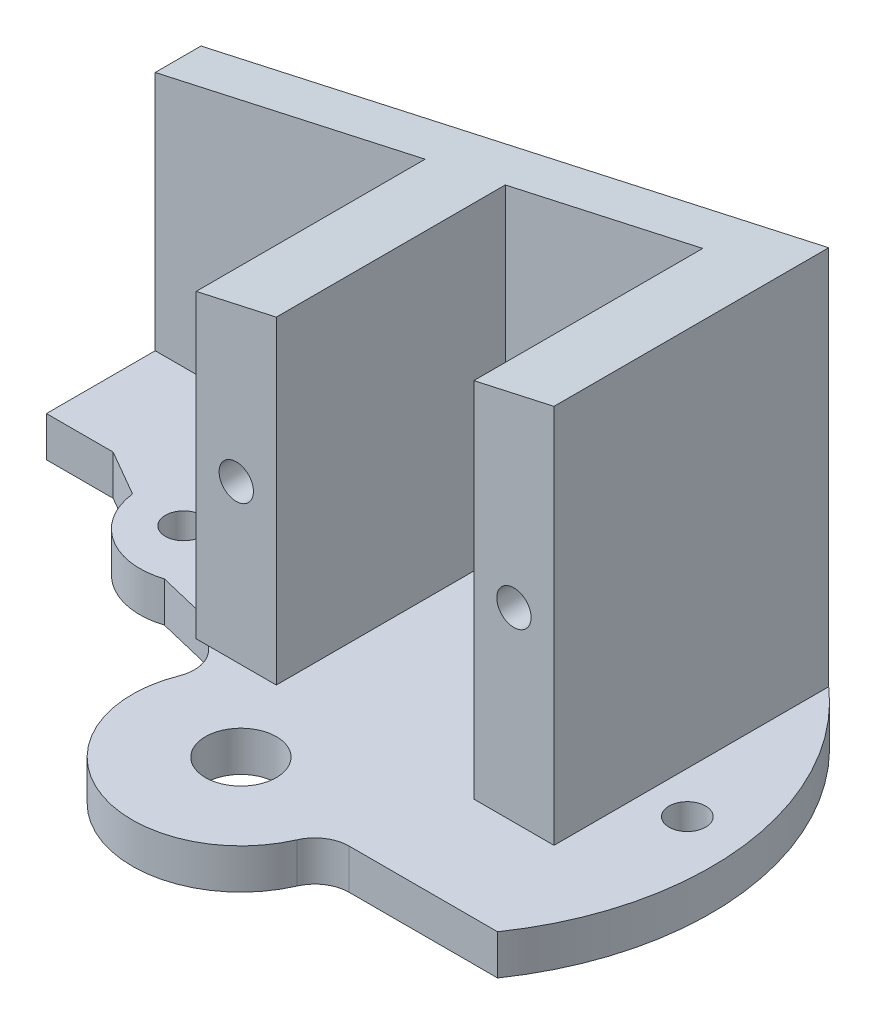
SolidWorks part; units mm, degrees
ref_plane "Alzado" through (0, 0, 0) normal (0, 0, 1) x (1, 0, 0)
ref_plane "Planta" through (0, 0, 0) normal (0, 1, 0) x (1, 0, 0)
ref_plane "Vista lateral" through (0, 0, 0) normal (1, 0, 0) x (0, 0, -1)
sketch "Croquis1" plane through (0, 0, 0) normal (0, 1, 0) x (1, 0, 0)
  line L0 (-35, 32.5) -> (35, -32.5) construction
  line L1 (-35, 32.5) -> (35, 32.5)
  line L2 (-35, 32.5) -> (-35, -32.5)
  line L3 (-35, -32.5) -> (35, -32.5)
  line L4 (35, 32.5) -> (35, -32.5)
  dimension "D1" = 70
  dimension "D2" = 65
extrude "Extruir1" add sketch "Croquis1" along normal blind 3.5
sketch "Croquis2" plane through (0, 3.5, 0) normal (0, 1, 0) x (1, 0, 0)
  line L0 (0, 32.5) -> (0, -32.5) construction
  line L1 (35, 32.5) -> (-35, 32.5) construction
  line L2 (-35, -32.5) -> (35, -32.5) construction
  circle A0 centre (0, -17.5) radius 3.1
  dimension "D1" = 6.2
  dimension "D2" = 15
extrude "Extruir2" cut sketch "Croquis2" against normal blind 5
sketch "Croquis3" plane through (0, 3.5, 0) normal (0, 1, 0) x (1, 0, 0)
  line L0 (0, -32.5) -> (0, 32.5) construction
  line L1 (-35, -32.5) -> (35, -32.5) construction
  line L2 (35, 32.5) -> (-35, 32.5) construction
  line L3 (-32.9868, -32.5) -> (-32.9868, 32.5) construction
  line L4 (-32.9868, 1.5) -> (-12.9615, 1.5)
  line L5 (18.8496, -32.5) -> (18.8496, 32.5) construction
  line L6 (-32.9868, 3.5) -> (18.8496, 3.5) construction
  line L7 (-32.9868, 2) -> (0, 2) construction
  line L8 (-32.9868, 11.5) -> (18.8496, 11.5) construction
  line L9 (0, -17.5) -> (-14.8492, -2.6508) construction
  line L10 (0, -17.5) -> (14.8492, -2.6508) construction
  line L11 (0, 2) -> (18.8496, 2) construction
  line L12 (-32.9868, 2) -> (18.8496, 2) construction
  line L13 (-32.9868, 12) -> (18.8496, 12)
  line L14 (-5.3033, -12.1967) -> (-16.2635, -1.2365) construction
  line L15 (12.9615, 1.5) -> (18.8496, 1.5)
  line L16 (-32.9868, 1.5) -> (18.8496, 1.5) construction
  line L17 (7.9844, -18) -> (22.9946, -18)
  line L18 (-5.9993, -12.2078) -> (-16.6132, -1.5939)
  line L19 (0, -17.5) -> (23, -17.5) construction
  line L20 (7.5, -17.5) -> (23, -17.5) construction
  line L21 (-5.6569, -12.5503) -> (-16.617, -1.5901) construction
  line L22 (7.5, -18) -> (23, -18) construction
  line L23 (-32.9868, 12) -> (-32.9868, 1.5)
  line L24 (18.8496, 12) -> (18.8496, 1.5)
  line L25 (-34.4868, 13.5) -> (20.3496, 13.5)
  line L26 (20.3496, 13.5) -> (20.3496, 0)
  line L27 (17.1464, 0) -> (20.3496, 0)
  line L28 (9.2871, -19.5) -> (24.4182, -19.5)
  line L29 (-7.9812, -12.3473) -> (-18.6805, -1.6479)
  line L30 (-34.4868, 0) -> (-17.1464, 0)
  line L31 (-34.4868, 13.5) -> (-34.4868, 0)
  circle A0 centre (0, -17.5) radius 21 construction
  circle A1 centre (0, -17.5) radius 7.5 construction
  arc A2 (-12.9615, 1.5) -> (-16.6132, -1.5939) centre (0, -17.5) ccw
  circle A3 centre (0, -17.5) radius 23 construction
  arc A4 (-5.9993, -12.2078) -> (7.9844, -18) centre (0, -17.5) ccw
  arc A5 (22.9946, -18) -> (12.9615, 1.5) centre (0, -17.5) ccw
  arc A6 (24.4182, -19.5) -> (17.1464, 0) centre (0, -17.5) ccw
  arc A7 (-7.9812, -12.3473) -> (9.2871, -19.5) centre (0, -17.5) ccw
  arc A8 (-17.1464, 0) -> (-18.6805, -1.6479) centre (0, -17.5) ccw
  dimension "D3" = 42
  dimension "D8" = 15
  dimension "D9" = 46
  dimension "D14" = 0.5
  dimension "D2" = 51.8364
  dimension "D6" = 90
  dimension "D7" = 45
  dimension "D1" = 32.9868
  dimension "D4" = 1.5
  dimension "D5" = 9.5
  dimension "D10" = 2
  dimension "D11" = 0.5
  dimension "D12" = 0.5
  dimension "D13" = 0.5
  dimension "D15" = 1.5
extrude "Extruir3" add sketch "Croquis3" along normal blind 10
sketch "Croquis4" plane through (0, 3.5, 0) normal (0, 1, 0) x (1, 0, 0)
  line L0 (-34.4868, 0) -> (-17.1464, 0) construction
  line L1 (-34.4868, 13.5) -> (-34.4868, 0) construction
  line L2 (20.3496, 13.5) -> (-34.4868, 13.5) construction
  line L3 (20.3496, 0) -> (20.3496, 13.5) construction
  line L4 (17.1464, 0) -> (20.3496, 0) construction
  line L5 (9.2871, -19.5) -> (24.4182, -19.5) construction
  line L6 (-18.6805, -1.6479) -> (-7.9812, -12.3473) construction
  line L7 (-34.4868, 0) -> (-17.1464, 0)
  line L8 (-34.4868, 13.5) -> (-34.4868, 0)
  line L9 (20.3496, 13.5) -> (-34.4868, 13.5)
  line L10 (20.3496, 0) -> (20.3496, 13.5)
  line L11 (17.1464, 0) -> (20.3496, 0)
  line L12 (9.2871, -19.5) -> (24.4182, -19.5)
  line L13 (-18.6805, -1.6479) -> (-7.9812, -12.3473)
  arc A0 (-17.1464, 0) -> (-18.6805, -1.6479) centre (0, -17.5) ccw construction
  arc A1 (24.4182, -19.5) -> (17.1464, 0) centre (0, -17.5) ccw construction
  arc A2 (-7.9812, -12.3473) -> (9.2871, -19.5) centre (0, -17.5) ccw construction
  arc A3 (-17.1464, 0) -> (-18.6805, -1.6479) centre (0, -17.5) ccw
  arc A4 (24.4182, -19.5) -> (17.1464, 0) centre (0, -17.5) ccw
  arc A5 (-7.9812, -12.3473) -> (9.2871, -19.5) centre (0, -17.5) ccw
extrude "Extruir4" cut sketch "Croquis4" against normal blind 10 flip side to cut
fillet "Redondeo1" radius 3 4 edges at (9.2871, 6.75, 19.5) (-7.9812, 6.75, 12.3473) (7.9844, 8.5, 18) (-5.9993, 8.5, 12.2078)
sketch "Croquis5" plane through (0, 0, 0) normal (0, -1, 0) x (1, 0, 0)
  line L0 (-18.6805, 1.6479) -> (-9.5151, 10.8133) construction
  line L1 (-34.4868, 0) -> (-17.1464, 0) construction
  line L2 (-18.6805, 1.6479) -> (-14.4379, 5.8906)
  line L3 (-24.4498, 0) -> (-17.1464, 0)
  line L4 (20.3496, 0) -> (20.3496, -13.5) construction
  line L5 (17.1464, 0) -> (20.3496, 0) construction
  line L6 (20.3496, 0) -> (20.3496, -13.5)
  line L7 (17.1464, 0) -> (20.3496, 0)
  arc A0 (-14.4379, 5.8906) -> (-24.4498, 0) centre (-18.6805, 1.6479) ccw
  arc A1 (-18.6805, 1.6479) -> (-17.1464, 0) centre (0, 17.5) ccw construction
  arc A2 (-18.6805, 1.6479) -> (-17.1464, 0) centre (0, 17.5) ccw
  arc A3 (24.4182, 19.5) -> (20.3496, -13.5) centre (3.8531, 5.2847) cw
  arc A4 (17.1464, 0) -> (24.4182, 19.5) centre (0, 17.5) ccw construction
  arc A5 (17.1464, 0) -> (24.4182, 19.5) centre (0, 17.5) ccw
  dimension "D1" = 12
  dimension "D2" = 25
extrude "Extruir5" add sketch "Croquis5" against normal up to surface (13.5 mm away) up to face at (-1.8278, 13.5, 5.5887)
chamfer "Chaflán1" distance 5 angle 45 2 edges at (-14.4379, 6.75, 5.8906) (-24.4498, 6.75, 0) first distance on face at (-20.5835, 6.75, 4.8823) first distance on face at (-29.4683, 6.75, 0)
sketch "Croquis6" plane through (0, 13.5, 0) normal (0, 1, 0) x (1, 0, 0)
  line L7 (-34.4868, 13.5) -> (-34.4868, 0)
  line L8 (-34.4868, 0) -> (-28.6614, 0)
  line L9 (-28.6614, 0) -> (-24.6424, -2.3231)
  line L10 (-16.83, -7.3554) -> (-11.7523, -8.5761)
  line L11 (-11.7523, -8.5761) -> (-9.5151, -10.8133)
  line L12 (11.4564, -19.5) -> (24.4182, -19.5)
  line L13 (20.3496, 13.5) -> (-34.4868, 13.5)
  line L14 (-34.4868, 13.5) -> (-34.4868, 0)
  line L15 (-34.4868, 0) -> (-28.6614, 0)
  line L16 (-28.6614, 0) -> (-24.6424, -2.3231)
  line L17 (-16.83, -7.3554) -> (-11.7523, -8.5761)
  line L18 (-11.7523, -8.5761) -> (-9.5151, -10.8133)
  line L19 (11.4564, -19.5) -> (24.4182, -19.5)
  line L20 (20.3496, 13.5) -> (-34.4868, 13.5)
  arc A5 (-24.6424, -2.3231) -> (-16.83, -7.3554) centre (-18.6805, -1.6479) ccw
  arc A6 (-8.8437, -14.0303) -> (-9.5151, -10.8133) centre (-11.6365, -12.9346) ccw
  arc A7 (-8.8437, -14.0303) -> (8.7069, -21.3) centre (0, -17.5) ccw
  arc A8 (11.4564, -19.5) -> (8.7069, -21.3) centre (11.4564, -22.5) ccw
  arc A9 (24.4182, -19.5) -> (20.3496, 13.5) centre (3.8531, -5.2847) ccw
  arc A10 (-24.6424, -2.3231) -> (-16.83, -7.3554) centre (-18.6805, -1.6479) ccw
  arc A11 (-8.8437, -14.0303) -> (-9.5151, -10.8133) centre (-11.6365, -12.9346) ccw
  arc A12 (-8.8437, -14.0303) -> (8.7069, -21.3) centre (0, -17.5) ccw
  arc A13 (11.4564, -19.5) -> (8.7069, -21.3) centre (11.4564, -22.5) ccw
  arc A14 (24.4182, -19.5) -> (20.3496, 13.5) centre (3.8531, -5.2847) ccw
  dimension "D1" = 0
extrude "Extruir6" add sketch "Croquis6" along normal blind 3.5 separate body
sketch "Croquis7" plane through (0, 17, 0) normal (0, 1, 0) x (1, 0, 0)
  line L0 (20.3496, 13.5) -> (-34.4868, 13.5) construction
  circle A0 centre (-20, -2.5) radius 1.6
  circle A1 centre (24, -2.5) radius 1.6
  dimension "D1" = 3.2
  dimension "D2" = 16
  dimension "D3" = 20
  dimension "D4" = 24
extrude "Extruir7" cut sketch "Croquis7" against normal through all
sketch "Croquis8" plane through (0, 17, 0) normal (0, 1, 0) x (1, 0, 0)
  circle A0 centre (0, -17.5) radius 3.1 construction
  circle A1 centre (0, -17.5) radius 3.1
extrude "Extruir8" cut sketch "Croquis8" against normal blind 5
sketch "Croquis9" plane through (0, 13.5, 0) normal (0, 1, 0) x (1, 0, 0)
  line L0 (18.8496, 1.5) -> (18.8496, 12) construction
  line L1 (18.8496, 1.5) -> (18.8496, 12)
  line L2 (19.5496, 1.5) -> (19.5496, 12)
  line L3 (18.8496, 12) -> (19.5496, 12)
  line L4 (18.8496, 1.5) -> (19.5496, 1.5)
  dimension "D1" = 0.7
extrude "Extruir9" cut sketch "Croquis9" against normal up to surface (10 mm away) up to face at (-1.6185, 3.5, 4.8365)
sketch "Croquis10" plane through (19.5496, 0, 0) normal (-1, 0, 0) x (0, 0, 1)
  line L0 (-5.875, 13.5) -> (-5.875, 3.5) construction
  line L3 (-1.5, 13.5) -> (-12, 13.5) construction
  line L4 (-12, 3.5) -> (-12, 13.5) construction
  line L5 (-5.875, 13.5) -> (-12, 3.5) construction
  line L6 (-12, 3.5) -> (-1.5, 3.5) construction
  line L7 (-8.9375, 8.5) -> (-12, 13.5) construction
  line L8 (19.5, 13.5) -> (-13.5, 13.5) construction
  line L10 (-7.4062, 11) -> (-10.4687, 11)
  line L11 (-7.4062, 11) -> (-7.4062, 6)
  line L12 (-7.4062, 6) -> (-10.4687, 6)
  line L13 (-10.4687, 11) -> (-10.4687, 6)
  dimension "D1" = 6.125
  dimension "D2" = 5
  dimension "D3" = 3.0625
extrude "Extruir10" cut sketch "Croquis10" against normal blind 10 and the other way through all
delete or keep bodies "Sólido-Eliminar1" type delete bodies bodies 111
sketch "Croquis11" plane through (0, 0, -13.5) normal (0, 0, -1) x (-1, 0, 0)
  line L0 (34.4868, 17) -> (34.4868, 38.056)
  line L1 (34.4868, 38.056) -> (-20.3496, 50.2129)
  line L2 (-20.3496, 50.2129) -> (-20.3496, 17)
  line L3 (-20.3496, 17) -> (34.4868, 17)
  dimension "D1" = 33.2129
  dimension "D2" = 21.056
extrude "Saliente-Extruir1" add sketch "Croquis11" against normal blind 4
sketch "Croquis13" plane through (0, 0, -9.5) normal (0, 0, 1) x (1, 0, 0)
  line L0 (-10.9056, 43.2838) -> (-3.9056, 44.8356)
  line L1 (-34.4868, 38.056) -> (20.3496, 50.2129) construction
  line L2 (-3.9056, 44.8356) -> (-3.9056, 17)
  line L3 (8.7069, 17) -> (-9.5, 17) construction
  line L4 (20.3496, 50.2129) -> (13.3496, 48.661)
  line L5 (13.3496, 48.661) -> (13.3496, 17)
  line L6 (-10.9056, 43.2838) -> (-10.9056, 17)
  line L7 (20.3496, 17) -> (-34.4868, 17) construction
  line L8 (-10.9056, 17) -> (-3.9056, 17)
  line L9 (13.3496, 17) -> (20.3496, 17)
  line L10 (20.3496, 17) -> (20.3496, 50.2129)
  dimension "D1" = 7
  dimension "D2" = 7
extrude "Saliente-Extruir2" add sketch "Croquis13" along normal blind 20
sketch "Croquis14" plane through (0, 0, 10.5) normal (0, 0, 1) x (1, 0, 0)
  line L0 (-10.9056, 30.2677) -> (-3.9056, 31.0155) construction
  line L2 (20.3496, 17) -> (20.3496, 50.2129) construction
  line L3 (-10.9056, 24.7363) -> (-10.9056, 33.6065) construction
  line L4 (-10.9056, 43.2838) -> (-10.9056, 17) construction
  line L5 (-3.9056, 24.7363) -> (-3.9056, 34.9948) construction
  line L6 (-3.9056, 17) -> (-3.9056, 44.8356) construction
  line L7 (-3.9056, 17) -> (-3.9056, 44.8356) construction
  line L8 (13.3496, 28.4054) -> (13.3496, 36.8668) construction
  line L9 (13.3496, 48.661) -> (13.3496, 17) construction
  line L10 (13.3496, 32.8587) -> (20.3496, 33.6065) construction
  circle A0 centre (-7.4056, 30.6416) radius 1.5
  circle A1 centre (16.8496, 33.2326) radius 1.5
  dimension "D1" = 3
  dimension "D2" = 3
extrude "Cortar-Extruir2" cut sketch "Croquis14" against normal blind 65
